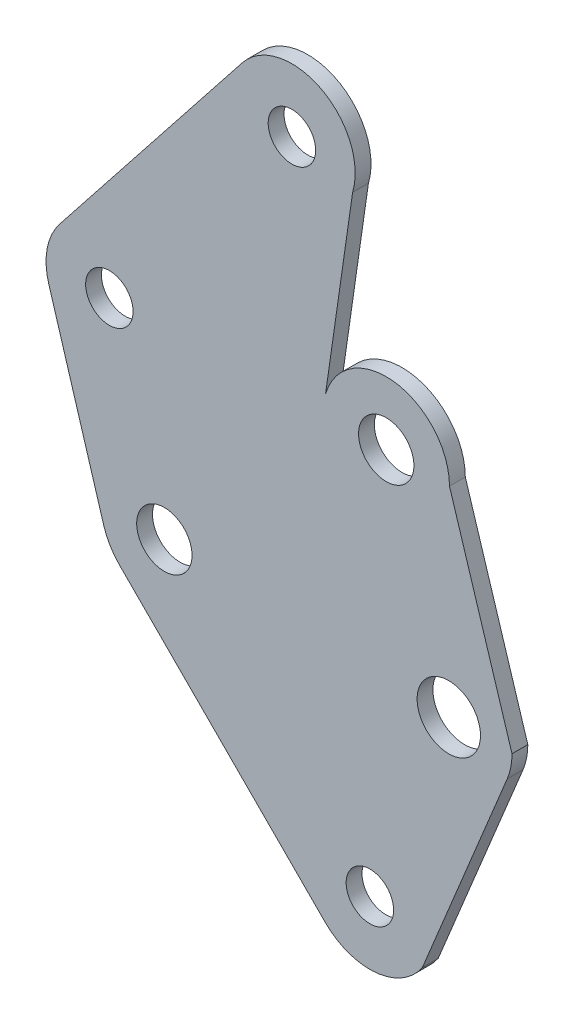
SolidWorks part; units mm, degrees
material "7075-O (SS)"
ref_plane "Front" through (0, 0, 0) normal (0, 0, 1) x (1, 0, 0)
ref_plane "Top" through (0, 0, 0) normal (0, 1, 0) x (1, 0, 0)
ref_plane "Right" through (0, 0, 0) normal (1, 0, 0) x (0, 0, -1)
sketch "草图1" plane through (0, 0, 0) normal (0, 0, 1) x (1, 0, 0)
  line L11 (480.9661, -500.4832) -> (492.5096, -485.8839) construction
  line L31 (494.6058, -527.8392) -> (481.6096, -514.7911)
  line L32 (500.7606, -527.2463) -> (506.1241, -514.2356)
  line L33 (496.3477, -487.0122) -> (494.6352, -498.9096)
  line L34 (502.4728, -500.0378) -> (506.4259, -512.712)
  line L35 (477.8284, -498.0024) -> (489.3715, -483.4028)
  line L36 (480.6153, -513.1275) -> (477.1377, -501.6424)
  circle A19 centre (480.9661, -500.4832) radius 1.5
  circle A21 centre (484.4437, -511.9683) radius 1.75
  circle A27 centre (492.5096, -485.8839) radius 1.5
  circle A34 centre (502.4283, -512.712) radius 2.0039
  circle A35 centre (497.4398, -525.0164) radius 1.5
  circle A36 centre (498.4728, -500.0378) radius 1.75
  circle A37 centre (524.4095, -513.6211) radius 1.5 construction
  arc A43 (496.3477, -487.0122) -> (489.3715, -483.4028) centre (492.5096, -485.8839) ccw
  arc A44 (477.8284, -498.0024) -> (477.1377, -501.6424) centre (480.9661, -500.4832) ccw
  arc A45 (506.1241, -514.2356) -> (506.4259, -512.712) centre (502.4283, -512.712) ccw
  arc A46 (494.6058, -527.8392) -> (500.7606, -527.2463) centre (497.4398, -525.0164) ccw
  arc A47 (502.4728, -500.0378) -> (494.6352, -498.9096) centre (498.4728, -500.0378) ccw
  arc A48 (480.6153, -513.1275) -> (481.6096, -514.7911) centre (484.4437, -511.9683) ccw
  dimension "D1" = 3.5
  dimension "D2" = 3.5
extrude "凸台-拉伸1" add sketch "草图1" along normal blind 1
